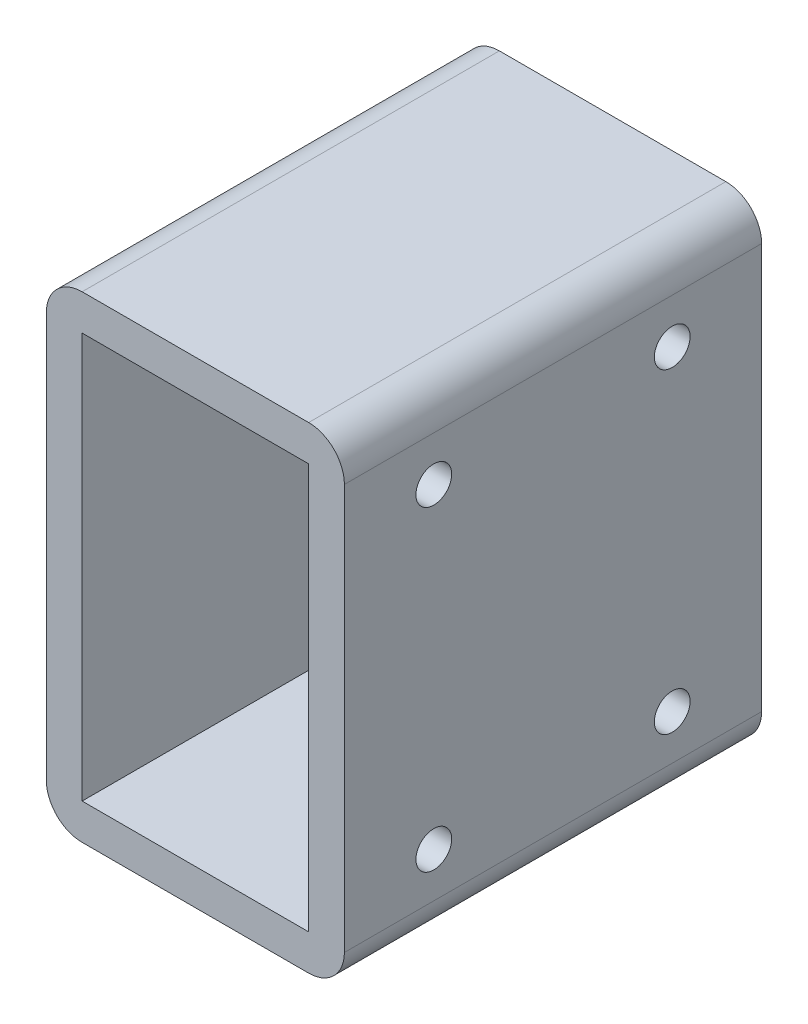
SolidWorks part; units mm, degrees
ref_plane "Front Plane" through (0, 0, 0) normal (0, 0, 1) x (1, 0, 0)
ref_plane "Top Plane" through (0, 0, 0) normal (0, 1, 0) x (1, 0, 0)
ref_plane "Right Plane" through (0, 0, 0) normal (1, 0, 0) x (0, 0, -1)
sketch "Sketch1" plane through (0, 0, 0) normal (0, 0, 1) x (1, 0, 0)
  line L0 (19, 34) -> (-19, 34)
  line L1 (19, -40) -> (-19, -40)
  line L2 (25, -34) -> (25, 34)
  line L3 (19, 40) -> (-19, 40)
  line L4 (-25, -34) -> (-25, 34)
  line L5 (25, -40) -> (-25, 40) construction
  line L6 (25, 40) -> (-25, -40) construction
  line L7 (-19, -34) -> (-19, 34)
  line L8 (19, -34) -> (-19, -34)
  line L9 (19, -34) -> (19, 34)
  arc A0 (-19, -40) -> (-25, -34) centre (-19, -34) cw
  arc A1 (19, -40) -> (25, -34) centre (19, -34) ccw
  arc A2 (25, 34) -> (19, 40) centre (19, 34) ccw
  arc A3 (-19, 40) -> (-25, 34) centre (-19, 34) ccw
  arc A4 (-19, 34) -> (-19, 34) centre (-19, 34) ccw
  arc A5 (-19, -34) -> (-19, -34) centre (-19, -34) cw
  arc A6 (19, -34) -> (19, -34) centre (19, -34) ccw
  arc A7 (19, 34) -> (19, 34) centre (19, 34) ccw
  point P0 (0, 0)
  dimension "D1" = 6
  dimension "D3" = 80
  dimension "D4" = 50
  dimension "D2" = 6
extrude "Boss-Extrude1" add sketch "Sketch1" along normal mid plane 70
sketch "Sketch2" plane through (25, 0, 0) normal (1, 0, 0) x (0, 0, -1)
  line L1 (20, -26.5) -> (-20, -26.5) construction
  line L2 (20, -26.5) -> (20, 26.5) construction
  line L3 (20, 26.5) -> (-20, 26.5) construction
  line L4 (-20, -26.5) -> (-20, 26.5) construction
  line L5 (20, -26.5) -> (-20, 26.5) construction
  line L6 (20, 26.5) -> (-20, -26.5) construction
  circle A0 centre (-20, 26.5) radius 3
  circle A1 centre (20, 26.5) radius 3
  circle A2 centre (20, -26.5) radius 3
  circle A3 centre (-20, -26.5) radius 3
  point P0 (0, 0)
  dimension "D3" = 6
  dimension "D1" = 40
  dimension "D2" = 53
extrude "Cut-Extrude1" cut sketch "Sketch2" against normal blind 10
equation "\"M5_tap\"=4.2mm"
equation "\"M5_clearence\"=5.5mm"
equation "\"M6_tap\"=5mm"
equation "\"M6_clearence\"=6.6mm"
equation "\"work_area_width\"=1100mm"
equation "\"work_area_depth\"=900mm"
equation "\"D3@Sketch1\"=\"steel_rollers_width\""
equation "\"D4@Sketch1\"=\"steel_rollers_height\""
equation "\"D1@Sketch1\"=\"steel_rollers_radius\""
equation "\"D2@Sketch1\"=\"steel_rollers_wall_thickness\""
equation "\"D1@Boss-Extrude1\"=\"work_area_depth\" + 200"
equation "\"steel_base_width\"=80mm"
equation "\"steel_base_height\"=50mm"
equation "\"steel_base_wall_thickness\"=3mm"
equation "\"steel_base_radius\"=6mm"
equation "\"steel_sides_width\"=180mm"
equation "\"steel_sides_height\"=50mm"
equation "\"steel_sides_wall_thickness\"=5mm"
equation "\"steel_sides_radius\"=6mm"
equation "\"steel_gantry_width\"=120mm"
equation "\"steel_gantry_height\"=80mm"
equation "\"steel_gantry_wall_thickness\"=6mm"
equation "\"steel_gantry_radius\"=6mm"
equation "\"steel_rollers_width\"=80mm"
equation "\"steel_rollers_height\"=50mm"
equation "\"steel_rollers_wall_thickness\"=6mm"
equation "\"steel_rollers_radius\"=6mm"
equation "\"steel_zbox_width\"=400mm"
equation "\"steel_zbox_height\"=90mm"
equation "\"steel_zbox_wall_thickness\"=3mm"
equation "\"steel_zbox_radius\"=6mm"
